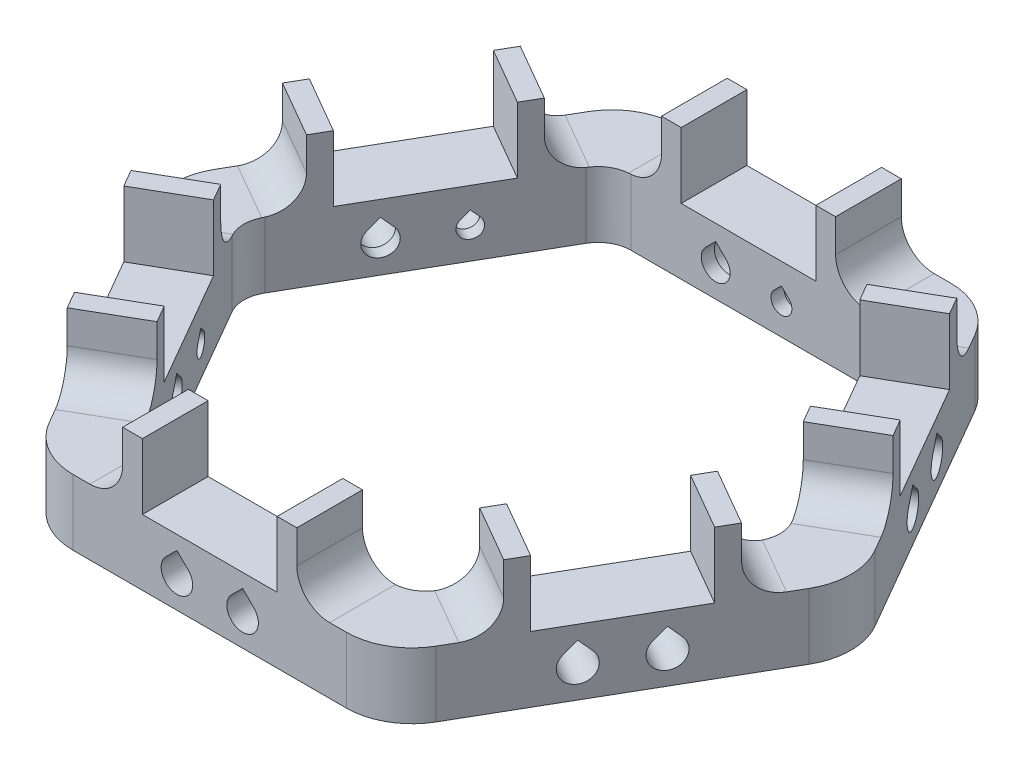
SolidWorks part; units mm, degrees
ref_plane "前基準面" through (0, 0, 0) normal (0, 0, 1) x (1, 0, 0)
ref_plane "上基準面" through (0, 0, 0) normal (0, 1, 0) x (1, 0, 0)
ref_plane "右基準面" through (0, 0, 0) normal (1, 0, 0) x (0, 0, -1)
sketch "草圖1" plane through (0, 0, 0) normal (0, 1, 0) x (1, 0, 0)
  line L0 (-20.7846, 36) -> (-41.5692, 0)
  line L1 (53.1162, 0) -> (26.5581, 46)
  line L2 (26.5581, 46) -> (-26.5581, 46)
  line L3 (-26.5581, 46) -> (-53.1162, 0)
  line L4 (-53.1162, 0) -> (-26.5581, -46)
  line L5 (-26.5581, -46) -> (26.5581, -46)
  line L6 (26.5581, -46) -> (53.1162, 0)
  line L7 (-41.5692, 0) -> (-20.7846, -36)
  line L8 (-20.7846, -36) -> (20.7846, -36)
  line L9 (20.7846, -36) -> (41.5692, 0)
  line L10 (41.5692, 0) -> (20.7846, 36)
  line L11 (20.7846, 36) -> (-20.7846, 36)
  circle A0 centre (0, 0) radius 46 construction
  dimension "D1" = 92
  dimension "D2" = 10
extrude "填料-伸長1" add sketch "草圖1" along normal blind 10
sketch "草圖2" plane through (-39.8372, 0, 23) normal (-0.866, 0, 0.5) x (0.5, 0, 0.866)
  line L0 (-5, 4.5) -> (5, 4.5) construction
  line L1 (-26.5581, 0) -> (26.5581, 0) construction
  line L2 (-5, 7.8941) -> (-6.6971, 6.1971)
  line L3 (-5, 7.8941) -> (-3.3029, 6.1971)
  line L4 (3.3029, 6.1971) -> (5, 7.8941)
  line L5 (5, 7.8941) -> (6.6971, 6.1971)
  arc A0 (-6.6971, 6.1971) -> (-3.3029, 6.1971) centre (-5, 4.5) ccw
  arc A1 (3.3029, 6.1971) -> (6.6971, 6.1971) centre (5, 4.5) ccw
  point P4 (0, 4.5)
  dimension "D2" = 4.8
  dimension "D3" = 4.8
  dimension "D1" = 10
  dimension "D4" = 4.5
extrude "除料-伸長1" cut sketch "草圖2" against normal blind 8
sketch "草圖3" plane through (-32.909, 0, 19) normal (-0.866, 0, 0.5) x (0.5, 0, 0.866)
  line L6 (-3.8686, 5.6314) -> (-5, 6.7627)
  line L7 (-5, 6.7627) -> (-6.1314, 5.6314)
  line L8 (-3.8686, 5.6314) -> (-5, 6.7627)
  line L9 (-5, 6.7627) -> (-6.1314, 5.6314)
  line L12 (6.5556, 6.0556) -> (5, 7.6113)
  line L13 (5, 7.6113) -> (3.4444, 6.0556)
  line L14 (6.5556, 6.0556) -> (5, 7.6113)
  line L15 (5, 7.6113) -> (3.4444, 6.0556)
  arc A3 (-6.1314, 5.6314) -> (-3.8686, 5.6314) centre (-5, 4.5) ccw
  arc A4 (-6.1314, 5.6314) -> (-3.8686, 5.6314) centre (-5, 4.5) ccw
  arc A6 (3.4444, 6.0556) -> (6.5556, 6.0556) centre (5, 4.5) ccw
  arc A7 (3.4444, 6.0556) -> (6.5556, 6.0556) centre (5, 4.5) ccw
  dimension "D1" = 0.8
  dimension "D2" = 0.2
extrude "除料-伸長2" cut sketch "草圖3" against normal blind 5
ref_axis "基準軸1" through (0, 10.5, 0) along (0, -1, 0)
pattern_circular "環狀複製排列1" count 6 over 360 about axis through (0, 10.5, 0) along (0, -1, 0) of "除料-伸長2", "除料-伸長1"
sketch "草圖4" plane through (0, 10, 0) normal (0, 1, 0) x (1, 0, 0)
  line L0 (0, 0) -> (-26.5581, -46)
  line L1 (-26.5581, -46) -> (26.5581, -46) construction
ref_plane "平面1" through (-26.5581, 10, 46) normal (-0.5, 0, 0.866) x (0.866, 0, 0.5)
sketch "草圖6" plane through (0, 10, 0) normal (0, 1, 0) x (1, 0, 0)
  line L0 (26.5581, 46) -> (-26.5581, 46) construction
  line L1 (-10.25, 46) -> (10.25, 46)
  line L2 (-10.25, 46) -> (-10.25, 36)
  line L3 (-10.25, 36) -> (10.25, 36)
  line L4 (10.25, 46) -> (10.25, 36)
  line L5 (20.7846, 36) -> (-20.7846, 36) construction
  line L7 (10.25, 46) -> (13.25, 46)
  line L8 (10.25, 46) -> (10.25, 36)
  line L9 (10.25, 36) -> (13.25, 36)
  line L10 (13.25, 46) -> (13.25, 36)
  line L11 (-10.25, 46) -> (-13.25, 46)
  line L12 (-10.25, 46) -> (-10.25, 36)
  line L13 (-10.25, 36) -> (-13.25, 36)
  line L14 (-13.25, 46) -> (-13.25, 36)
  point P8 (0, 36)
  line M9 (26.5581, 46) -> (-26.5581, 46)
  line M14 (-20.7846, 36) -> (20.7846, 36)
  dimension "D1" = 20.5
  dimension "D2" = 3
  dimension "D3" = 3
extrude "填料-伸長2" add sketch "草圖6" along normal blind 10 contours L14 L2 M9 M14 | L10 L4 M9 M14 region at (-11.75, 10, -41) region at (11.75, 10, -41)
fillet "圓角4" radius 5 2 edges at (13.25, 10, -41) (-13.25, 10, -41)
pattern_circular "環狀複製排列3" count 6 over 360 about axis through (0, 10.5, 0) along (0, -1, 0) of "圓角4", "填料-伸長2"
fillet "圓角5" radius 10 6 edges at (26.5581, 5, -46) (-26.5581, 5, -46) (-53.1162, 5, 0) (-26.5581, 5, 46) (26.5581, 5, 46) (53.1162, 5, 0)
fillet "圓角6" radius 5 6 edges at (-20.7846, 5, 36) (-41.5692, 5, 0) (-20.7846, 5, -36) (20.7846, 5, -36) (41.5692, 5, 0) (20.7846, 5, 36)
chamfer "導角1" [suppressed] distance 1 angle 45
